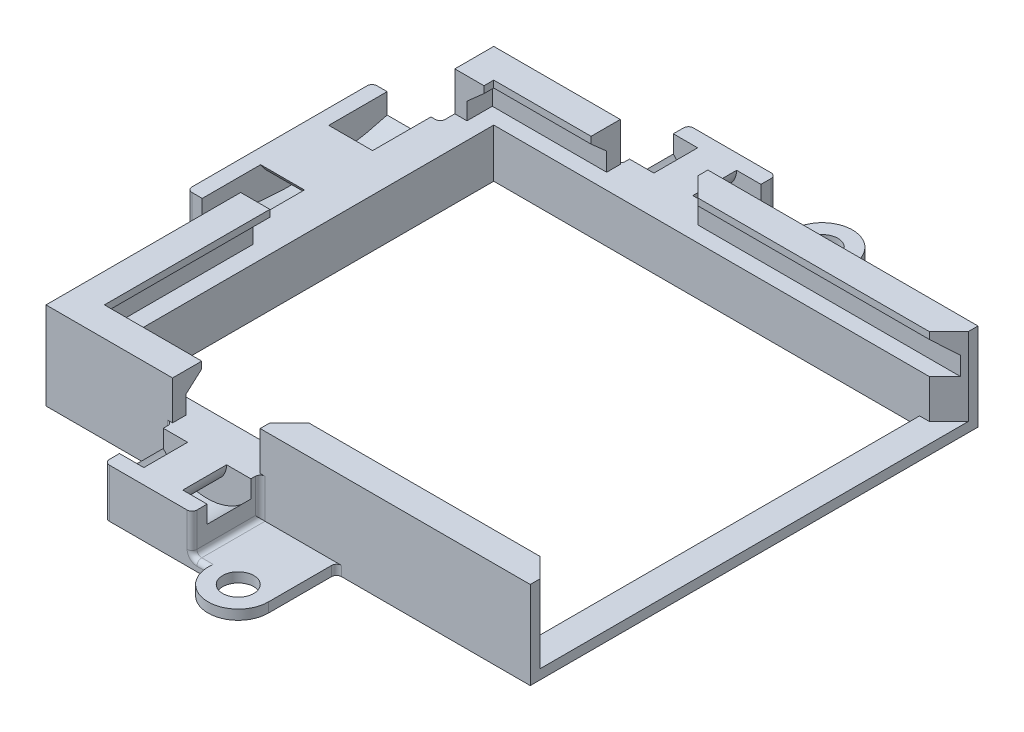
SolidWorks part; units mm, degrees
ref_plane "Alzado" through (0, 0, 0) normal (0, 0, 1) x (1, 0, 0)
ref_plane "Planta" through (0, 0, 0) normal (0, 1, 0) x (1, 0, 0)
ref_plane "Vista lateral" through (0, 0, 0) normal (1, 0, 0) x (0, 0, -1)
sketch "Croquis1" plane through (0, 0, 0) normal (0, 1, 0) x (1, 0, 0)
  line L0 (4.975, -30) -> (4.975, -23)
  line L1 (-21.875, -20) -> (21.875, -20)
  line L2 (-21.875, -20) -> (-21.875, 20)
  line L3 (-21.875, 20) -> (21.875, 20)
  line L4 (21.875, -20) -> (21.875, 20)
  line L5 (-21.875, -20) -> (21.875, 20) construction
  line L6 (-21.875, 20) -> (21.875, -20) construction
  line L7 (-24.875, -23) -> (-11.875, -23)
  line L8 (-24.875, -23) -> (-24.875, 23)
  line L9 (-24.875, 23) -> (-11.875, 23)
  line L10 (24.875, -23) -> (24.875, 23)
  line L11 (-24.875, -23) -> (24.875, 23) construction
  line L12 (-24.875, 23) -> (24.875, -23) construction
  line L13 (-11.875, 23) -> (-11.875, 30)
  line L14 (4.975, -23) -> (24.875, -23)
  line L15 (0, 0) -> (21.875, 0) construction
  line L17 (4.975, 30) -> (4.975, 23)
  line L18 (4.975, 23) -> (24.875, 23)
  line L19 (-1.225, 30) -> (-11.875, 30)
  line L22 (-1.225, -30) -> (-11.875, -30)
  line L23 (-11.875, -23) -> (-11.875, -30)
  circle A0 centre (1.875, -30) radius 1.6
  arc A1 (-1.225, -30) -> (4.975, -30) centre (1.875, -30) ccw
  arc A2 (-1.225, 30) -> (4.975, 30) centre (1.875, 30) cw
  circle A3 centre (1.875, 30) radius 1.6
  point P0 (0, 0)
  point P6 (0, 0)
  dimension "D7" = 6.2
  dimension "D8" = 3.2
  dimension "D1" = 43.75
  dimension "D2" = 40
  dimension "D3" = 3
  dimension "D4" = 3
  dimension "D5" = 10
  dimension "D6" = 20
  dimension "D9" = 13.75
extrude "Saliente-Extruir1" add sketch "Croquis1" along normal blind 1
sketch "Croquis2" plane through (0, 1, 0) normal (0, 1, 0) x (1, 0, 0)
  line L0 (21.875, -20) -> (24.875, -20)
  line L1 (-24.875, 23) -> (24.875, 23)
  line L2 (-24.875, 23) -> (-24.875, -23)
  line L3 (-24.875, -23) -> (24.875, -23)
  line L4 (24.875, 23) -> (24.875, 20)
  line L5 (-21.875, 20) -> (21.875, 20)
  line L6 (-21.875, 20) -> (-21.875, -20)
  line L7 (-21.875, -20) -> (21.875, -20)
  line L9 (21.875, 20) -> (24.875, 20)
  line L10 (24.875, -20) -> (24.875, -23)
  dimension "D1" = 3
extrude "Saliente-Extruir2" add sketch "Croquis2" along normal blind 8
sketch "Croquis3" plane through (24.875, 0, 0) normal (-1, 0, 0) x (0, 0, 1)
  line L0 (-23, 0) -> (23, 0) construction
  line L1 (21.6, 5) -> (-21.6, 5)
  line L2 (21.6, 5) -> (21.6, 6.8)
  line L3 (21.6, 6.8) -> (-21.6, 6.8)
  line L4 (-21.6, 5) -> (-21.6, 6.8)
  line L5 (21.6, 5) -> (-21.6, 6.8) construction
  line L6 (21.6, 6.8) -> (-21.6, 5) construction
  point P0 (0, 5.9)
  dimension "D1" = 5
  dimension "D2" = 1.8
  dimension "D3" = 43.2
extrude "Cortar-Extruir1" cut sketch "Croquis3" along normal blind 48.5
chamfer "Chaflán1" distance 1.5 distance2 1.7 3 edges at (1.5, 6.8, -20) (1.5, 6.8, 20) (-21.875, 6.8, 0)
sketch "Croquis4" plane through (0, 9, 0) normal (0, 1, 0) x (1, 0, 0)
  line L1 (-21.875, 20) -> (-21.875, -20) construction
  line L2 (-11.875, -20) -> (-2.875, -20)
  line L3 (-11.875, -20) -> (-11.875, -23)
  line L4 (-11.875, -23) -> (-2.875, -23)
  line L5 (-2.875, -20) -> (-2.875, -23)
  line L6 (-11.875, -20) -> (-2.875, -23) construction
  line L7 (-11.875, -23) -> (-2.875, -20) construction
  line L10 (-11.875, -23) -> (4.975, -23) construction
  line L12 (0, 0) -> (-21.875, 0) construction
  line L13 (-11.875, 23) -> (-2.875, 20) construction
  line L14 (-11.875, 20) -> (-2.875, 23) construction
  line L15 (-2.875, 20) -> (-2.875, 23)
  line L16 (-11.875, 23) -> (-2.875, 23)
  line L17 (-11.875, 20) -> (-11.875, 23)
  line L18 (-11.875, 20) -> (-2.875, 20)
  line L19 (24.875, -20) -> (-21.875, -20) construction
  point P0 (-7.375, -21.5)
  point P18 (-7.375, 21.5)
  dimension "D1" = 10
  dimension "D2" = 9
extrude "Cortar-Extruir3" cut sketch "Croquis4" against normal blind 4
chamfer "Chaflán2" distance 2 distance2 2 4 edges at (-2.875, 8.65, -20) (-2.875, 8.65, 20) (24.875, 8.65, -20) (24.875, 8.65, 20)
sketch "Croquis5" plane through (0, 1, 0) normal (0, 1, 0) x (1, 0, 0)
  line L0 (-2.875, 22) -> (-2.875, 23) construction
  line L1 (-11.875, 30) -> (-2.875, 30)
  line L2 (-11.875, 30) -> (-11.875, 23)
  line L3 (-11.875, 23) -> (-2.875, 23)
  line L4 (-2.875, 30) -> (-2.875, 23)
  line L5 (-11.875, 30) -> (-2.875, 23) construction
  line L6 (-11.875, 23) -> (-2.875, 30) construction
  line L7 (-11.875, 23) -> (-11.875, 20) construction
  line L9 (4.975, 23) -> (-11.875, 23) construction
  line L10 (-1.225, 30) -> (-11.875, 30) construction
  line L11 (0, 0) -> (-24.875, 0) construction
  line L13 (-11.875, -23) -> (-2.875, -30) construction
  line L14 (-11.875, -30) -> (-2.875, -23) construction
  line L15 (-2.875, -30) -> (-2.875, -23)
  line L16 (-11.875, -23) -> (-2.875, -23)
  line L17 (-11.875, -30) -> (-11.875, -23)
  line L18 (-11.875, -30) -> (-2.875, -30)
  line L19 (-24.875, 23) -> (-24.875, -23) construction
  point P0 (-7.375, 26.5)
  point P25 (-7.375, -26.5)
extrude "Saliente-Extruir3" add sketch "Croquis5" along normal blind 4
ref_plane "Plano1" through (0, 0, -26.2) normal (0, 0, -1) x (-1, 0, 0)
sketch "Croquis8" plane through (0, 0, -26.2) normal (0, 0, -1) x (-1, 0, 0)
  line L0 (2.875, 5) -> (2.875, 1) construction
  line L1 (2.875, 5) -> (11.875, 5) construction
  line L2 (2.875, 9) -> (11.875, 9) construction
  line L3 (11.875, 5) -> (11.875, 0) construction
  line L5 (2.875, 7) -> (11.875, 7) construction
  line L8 (2.875, 5) -> (2.875, 3.2)
  line L9 (2.875, 5) -> (5.375, 5)
  line L10 (2.875, 5) -> (2.875, 9) construction
  line L11 (11.875, 5) -> (11.875, 9) construction
  line L12 (9.375, 5) -> (11.875, 5)
  line L13 (11.875, 5) -> (11.875, 3.2)
  arc A0 (5.375, 5) -> (9.375, 5) centre (7.375, 5) ccw
  arc A1 (2.875, 3.2) -> (11.875, 3.2) centre (7.375, 6.7023) ccw
  point P8 (0, 0)
  point P9 (7.375, 3)
  point P10 (7.375, 5)
  point P18 (7.375, 1)
  dimension "D2" = 2
  dimension "D1" = 2.5
  dimension "D3" = 2
  dimension "D4" = 1.8
  dimension "D5" = 1.8
extrude "Cortar-Extruir7" cut sketch "Croquis8" against normal mid plane 4.5
mirror "Simetría1" about plane through (0, 0, 0) normal (0, 0, 1) of "Cortar-Extruir7"
sketch "Croquis9" plane through (0, 0, 0) normal (0, 1, 0) x (1, 0, 0)
  line L0 (-21.875, 20) -> (-21.875, -20) construction
  line L1 (-21.875, 17.5) -> (-31.875, 17.5)
  line L2 (-21.875, 17.5) -> (-21.875, -1.5)
  line L3 (-21.875, -1.5) -> (-31.875, -1.5)
  line L4 (-31.875, 17.5) -> (-31.875, -1.5)
  line L5 (21.875, 20) -> (22.875, 20) construction
  point P8 (22.375, 20)
  dimension "D1" = 2.5
  dimension "D2" = 19
  dimension "D3" = 10
extrude "Saliente-Extruir4" add sketch "Croquis9" along normal blind 5
sketch "Croquis10" plane through (0, 9, 0) normal (0, 1, 0) x (1, 0, 0)
  line L0 (-24.875, 23) -> (-24.875, -23) construction
  line L1 (-24.875, 19) -> (-21.875, 19)
  line L2 (-24.875, 19) -> (-24.875, -3)
  line L3 (-24.875, -3) -> (-21.875, -3)
  line L4 (-21.875, 19) -> (-21.875, -3)
  line L5 (-21.875, -20) -> (-21.875, 20) construction
  line L6 (-24.875, 17.5) -> (-31.875, 17.5) construction
  line L7 (-31.875, -1.5) -> (-24.875, -1.5) construction
  point P10 (-28.375, 17.5)
  dimension "D1" = 1.5
  dimension "D2" = 1.5
extrude "Cortar-Extruir5" cut sketch "Croquis10" against normal blind 4
ref_plane "Plano3" through (-28.075, 0, 0) normal (-1, 0, 0) x (0, 0, 1)
sketch "Croquis11" plane through (-28.075, 0, 0) normal (-1, 0, 0) x (0, 0, 1)
  line L0 (-17.5, 5) -> (-17.5, 0) construction
  line L1 (-17.5, 5) -> (1.5, 5) construction
  line L2 (1.5, 5) -> (1.5, 0) construction
  line L3 (-17.5, 5) -> (-17.5, 2.9139)
  line L4 (1.5, 5) -> (1.5, 2.9139)
  line L5 (-19, 5) -> (-17.5, 5) construction
  line L6 (-17.5, 5) -> (-17.5, 0) construction
  line L7 (-17.5, 5) -> (-11.5, 5)
  line L8 (-4.5, 5) -> (1.5, 5)
  arc A0 (-11.5, 5) -> (-4.5, 5) centre (-8, 7.0625) ccw
  arc A1 (-17.5, 2.9139) -> (1.5, 2.9139) centre (-8, 36.6) ccw
  point P5 (-8, 3)
  point P13 (-8, 5)
  point P15 (-8, 1.6)
  dimension "D1" = 2
  dimension "D2" = 6
  dimension "D4" = 35
  dimension "D3" = 1.4
fillet "Redondeo2" radius 0.5 19 edges at (-2.05, 1, 30) (-2.05, 1, -30) (-2.875, 3, 30) (-2.875, 1, 26.5) (-2.875, 3, 23) (-11.875, 2.5, 30) (-11.875, 2.5, 23) (-11.875, 2.5, -30) (-2.875, 3, -30) (-2.875, 1, -26.5) (1.05, 1, -23) (-2.875, 3, -23) (-11.875, 2.5, -23) (4.975, 0.5, 23) (4.975, 0.5, -23) (-24.875, 2.5, -17.5) (-31.875, 2.5, -17.5) (-24.875, 2.5, 1.5) (-31.875, 2.5, 1.5)
extrude "Cortar-Extruir8" cut sketch "Croquis11" against normal mid plane 4.5
